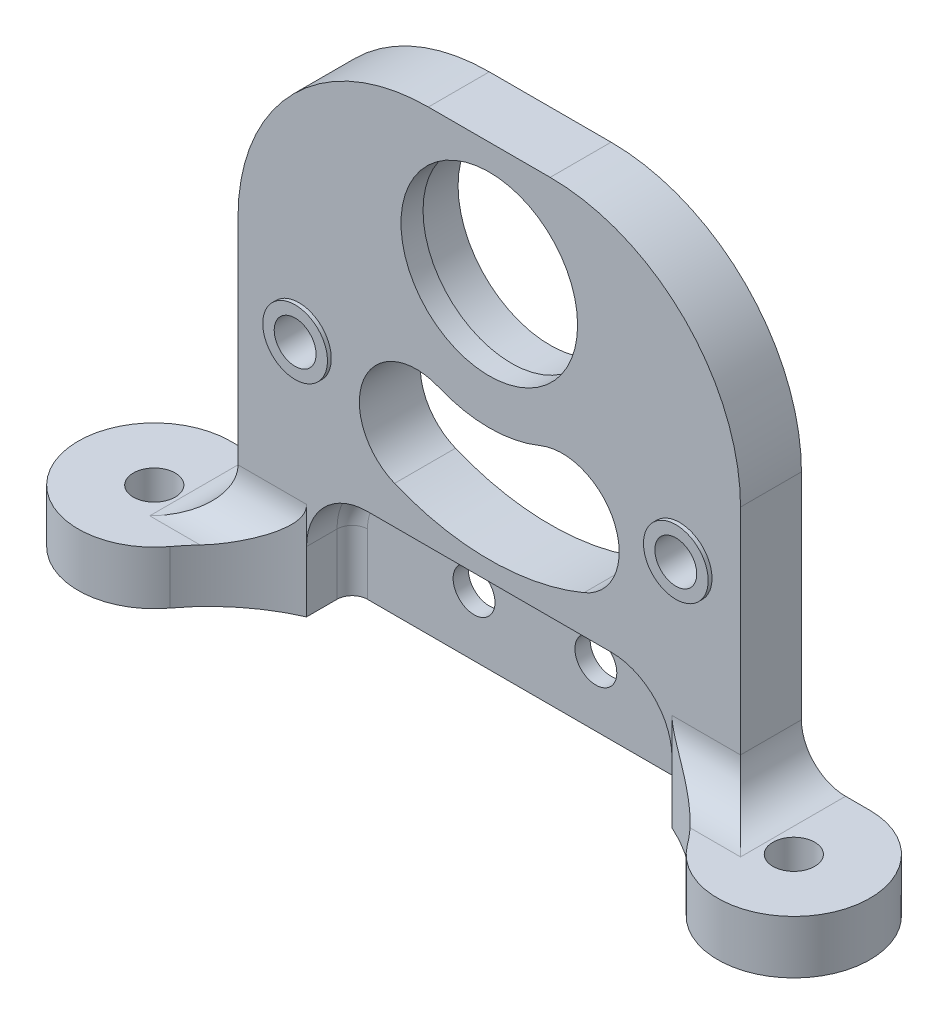
SolidWorks part; units mm, degrees
ref_plane "Front Plane" through (0, 0, 0) normal (0, 0, 1) x (1, 0, 0)
ref_plane "Top Plane" through (0, 0, 0) normal (0, 1, 0) x (1, 0, 0)
ref_plane "Right Plane" through (0, 0, 0) normal (1, 0, 0) x (0, 0, -1)
sketch "Sketch1" plane through (0, 0, 0) normal (0, 0, 1) x (1, 0, 0)
  line L1 (0, 15) -> (33, 15)
  line L2 (0, 15) -> (0, -51)
  line L3 (0, -51) -> (33, -51)
  line L4 (33, 15) -> (33, -51)
  point P5 (0, 0)
  dimension "D1" = 33
  dimension "D2" = 66
  dimension "D4" = 15
extrude "Boss-Extrude1" add sketch "Sketch1" along normal blind 8 separate body
sketch "Sketch3" plane through (0, 0, 8) normal (0, 0, 1) x (1, 0, 0)
  line L0 (0, 15) -> (0, -51) construction
  line L1 (33, 15) -> (0, 15) construction
  line L2 (9.5671, -23.097) -> (0, 0) construction
  line L3 (-17.5, 0) -> (-32.5, 0)
  line L4 (33, -51) -> (33, 15) construction
  line L5 (0, -51) -> (33, -51) construction
  circle A0 centre (25, -20) radius 2.75
  circle A1 centre (0, 0) radius 11.6
  arc A2 (-17.5, 0) -> (6.697, -16.1679) centre (0, 0) ccw
  arc A3 (-32.5, 0) -> (12.4372, -30.0261) centre (0, 0) ccw
  arc A4 (12.4372, -30.0261) -> (6.697, -16.1679) centre (9.5671, -23.097) ccw
  dimension "D1" = 5.5
  dimension "D2" = 23.2
  dimension "D4" = 35
  dimension "D5" = 65
  dimension "D3" = 15
  dimension "D6" = 22.5
  dimension "D7" = 8
  dimension "D8" = 31
extrude "Cut-Extrude1" cut sketch "Sketch3" against normal through all
sketch "Sketch4" plane through (0, 0, 8) normal (0, 0, 1) x (1, 0, 0)
  circle A0 centre (25, -20) radius 2.75 construction
  circle A1 centre (25, -20) radius 2.75
  circle A2 centre (25, -20) radius 4.25
  dimension "D1" = 8.5
extrude "Boss-Extrude3" add sketch "Sketch4" along normal blind 0.5
chamfer "Chamfer1" distance 2.5 angle 45 1 edges at (27.75, -20, 0)
sketch "Sketch6" plane through (0, 0, 0) normal (0, 0, -1) x (-1, 0, 0)
  circle A0 centre (0, 0) radius 12.1
  dimension "D1" = 24.2
extrude "Cut-Extrude2" cut sketch "Sketch6" against normal blind 5.1
fillet "Fillet4" radius 25 1 edges at (33, 15, 4)
sketch "Sketch10" plane through (0, -51, 0) normal (0, -1, 0) x (1, 0, 0)
  line L0 (42, 0) -> (32, 0)
  line L1 (0, 0) -> (33, 0) construction
  line L2 (32, 10) -> (32, 0)
  line L3 (33, 8) -> (33, 0) construction
  arc A0 (42, 0) -> (32, 10) centre (42, 10) ccw
  circle A1 centre (42, 10) radius 2.75
  point P7 (31.0917, 0)
  dimension "D1" = 5.5
  dimension "D2" = 20
  dimension "D3" = 1
extrude "Boss-Extrude4" add sketch "Sketch10" against normal blind 7
sketch "Sketch11" plane through (0, 0, 8) normal (0, 0, 1) x (1, 0, 0)
  line L1 (0, -51) -> (24, -51)
  line L2 (0, -51) -> (0, -35)
  line L3 (0, -35) -> (16, -35)
  line L4 (24, -51) -> (24, -43)
  arc A0 (16, -35) -> (24, -43) centre (16, -43) cw
  dimension "D1" = 8
  dimension "D2" = 16
  dimension "D3" = 24
extrude "Cut-Extrude3" cut sketch "Sketch11" against normal blind 6
sketch "Sketch12" plane through (0, 0, 2) normal (0, 0, 1) x (1, 0, 0)
  line L0 (8, -43) -> (0, -43) construction
  line L1 (0, -35) -> (0, -51) construction
  circle A0 centre (8, -43) radius 2.75
  point P2 (8.2093, -43)
  dimension "D1" = 5.5
  dimension "D2" = 8
extrude "Cut-Extrude4" cut sketch "Sketch12" against normal blind 6
fillet "Fillet7" radius 2 3 edges at (24, -47, 2) (8, -35, 2) (21.6569, -37.3431, 2)
fillet "Fillet5" radius 25 1 edges at (32, -47.5, 8)
fillet "Fillet6" radius 5.8 2 edges at (33, -44, 4) (28.5, -44, 8)
mirror "Mirror1" about plane through (0, 15, 8) normal (1, 0, 0) of bodies 111 105
ref_plane "Mid Plane" through (0, 0, 0) normal (1, 0, 0) x (0, 0, -1)
